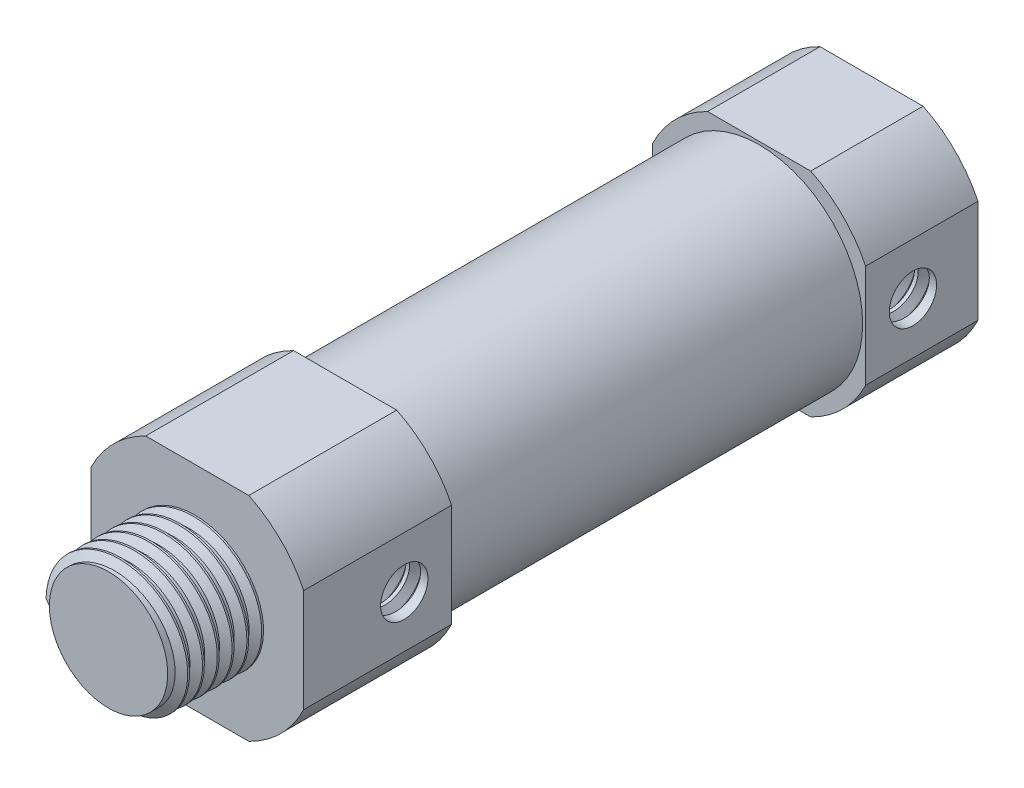
SolidWorks part; units mm, degrees
material "1060 合金"
ref_plane "前视基准面" through (0, 0, 0) normal (0, 0, 1) x (1, 0, 0)
ref_plane "上视基准面" through (0, 0, 0) normal (0, 1, 0) x (1, 0, 0)
ref_plane "右视基准面" through (0, 0, 0) normal (1, 0, 0) x (0, 0, -1)
sketch "草图1" plane through (0, 0, 0) normal (0, 0, 1) x (1, 0, 0)
  circle A0 centre (0, 0) radius 10
  dimension "D1" = 20
extrude "凸台-拉伸1" add sketch "草图1" along normal blind 9.5
sketch "草图2" plane through (0, 0, 9.5) normal (0, 0, 1) x (1, 0, 0)
  line L1 (-9, 9) -> (9, 9)
  line L2 (-9, 9) -> (-9, -9)
  line L3 (-9, -9) -> (9, -9)
  line L4 (9, 9) -> (9, -9)
  line L5 (-9, 9) -> (9, -9) construction
  line L6 (-9, -9) -> (9, 9) construction
  circle A0 centre (0, 0) radius 15
  point P0 (0, 0)
  dimension "D2" = 30
  dimension "D1" = 18
extrude "切除-拉伸1" cut sketch "草图2" against normal blind 9.5
sketch "草图3" plane through (0, 0, 9.5) normal (0, 0, 1) x (1, 0, 0)
  circle A0 centre (0, 0) radius 8.75
  dimension "D1" = 17.5
extrude "凸台-拉伸2" add sketch "草图3" along normal blind 35
sketch "草图4" plane through (0, 0, 44.5) normal (0, 0, 1) x (1, 0, 0)
  line L1 (9, -9) -> (-9, -9)
  line L2 (9, -9) -> (9, 9)
  line L3 (9, 9) -> (-9, 9)
  line L4 (-9, -9) -> (-9, 9)
  line L5 (9, -9) -> (-9, 9) construction
  line L6 (9, 9) -> (-9, -9) construction
  circle A0 centre (0, 0) radius 10
  circle M5 centre (0, 0) radius 8.75
  dimension "D1" = 20
  dimension "D2" = 18
extrude "凸台-拉伸3" add sketch "草图4" along normal blind 12.5 contours M5 | L2 A0 L3 L4 L1 M5 region at (0, -8.9745, 44.5) region at (0, 0, 44.5)
sketch "草图5" plane through (0, 0, 57) normal (0, 0, 1) x (1, 0, 0)
  circle A0 centre (0, 0) radius 5
  dimension "D1" = 10
extrude "凸台-拉伸4" add sketch "草图5" along normal blind 7.5
thread "螺纹线1" pitch 1.25 method extrude profile "螺纹线轮廓1" start angle 0, offset 0, length 7.5, pitch 1.25, diameter 10
ref_plane "基准面1" through (-5, 0, 64.5) normal (0, -1, 0) x (-1, 0, 0)
sketch "螺纹线轮廓1" plane through (-5, 0, 64.5) normal (0, -1, 0) x (-1, 0, 0)
  line L0 (0, 0) -> (0, 1.25) construction
  line L1 (0, 0) -> (0.6766, 0.3906)
  line L2 (0.6766, 0.3906) -> (0.6766, 0.5469)
  line L3 (0.6766, 0.5469) -> (0, 0.9375)
  line L4 (0.6766, 0.4687) -> (0, 0.4687) construction
  line L11 (0, 0) -> (0, 0.9375)
  point P2 (0, 0)
  dimension "Pitch" = 1.25
  dimension "Profile_Angle" = 60
  dimension "Profile_Land" = 0.1562
  dimension "Profile_Height" = 0.6766
sketch "草图11" plane through (9, 0, 0) normal (1, 0, 0) x (0, 0, -1)
  line L0 (-44.5, -4.3589) -> (-44.5, 4.3589) construction
  line L1 (-9.5, 8.75) -> (-9.5, -8.75) construction
  circle A0 centre (-48.5, 0) radius 2
  circle A1 centre (-5.5, 0) radius 2
  dimension "D1" = 4
  dimension "D2" = 4
  dimension "D3" = 4
  dimension "D4" = 4
extrude "切除-拉伸2" cut sketch "草图11" against normal blind 5
thread "螺纹线2" pitch 1.25 method cut profile "螺纹线轮廓2" start angle 0, offset 0, length 5, pitch 1.25, diameter 4
ref_plane "基准面2" through (9, 0, 50.5) normal (0, -1, 0) x (0, 0, 1)
sketch "螺纹线轮廓2" plane through (9, 0, 50.5) normal (0, -1, 0) x (0, 0, 1)
  line L0 (0, 0) -> (0, 1.25) construction
  line L1 (0, 0) -> (0.6766, 0.3906)
  line L2 (0.6766, 0.3906) -> (0.6766, 0.5469)
  line L3 (0.6766, 0.5469) -> (0, 0.9375)
  line L4 (0.6766, 0.4687) -> (0, 0.4687) construction
  line L11 (0, 0) -> (0, 0.9375)
  point P2 (0, 0)
  dimension "Pitch" = 1.25
  dimension "Profile_Angle" = 60
  dimension "Profile_Land" = 0.1562
  dimension "Profile_Height" = 0.6766
thread "螺纹线3" pitch 1.25 method cut profile "螺纹线轮廓3" start angle 0, offset 0, length 5, pitch 1.25, diameter 4
ref_plane "基准面3" through (9, 0, 7.5) normal (0, -1, 0) x (0, 0, 1)
sketch "螺纹线轮廓3" plane through (9, 0, 7.5) normal (0, -1, 0) x (0, 0, 1)
  line L0 (0, 0) -> (0, 1.25) construction
  line L1 (0, 0) -> (0.6766, 0.3906)
  line L2 (0.6766, 0.3906) -> (0.6766, 0.5469)
  line L3 (0.6766, 0.5469) -> (0, 0.9375)
  line L4 (0.6766, 0.4687) -> (0, 0.4687) construction
  line L11 (0, 0) -> (0, 0.9375)
  point P2 (0, 0)
  dimension "Pitch" = 1.25
  dimension "Profile_Angle" = 60
  dimension "Profile_Land" = 0.1562
  dimension "Profile_Height" = 0.6766
